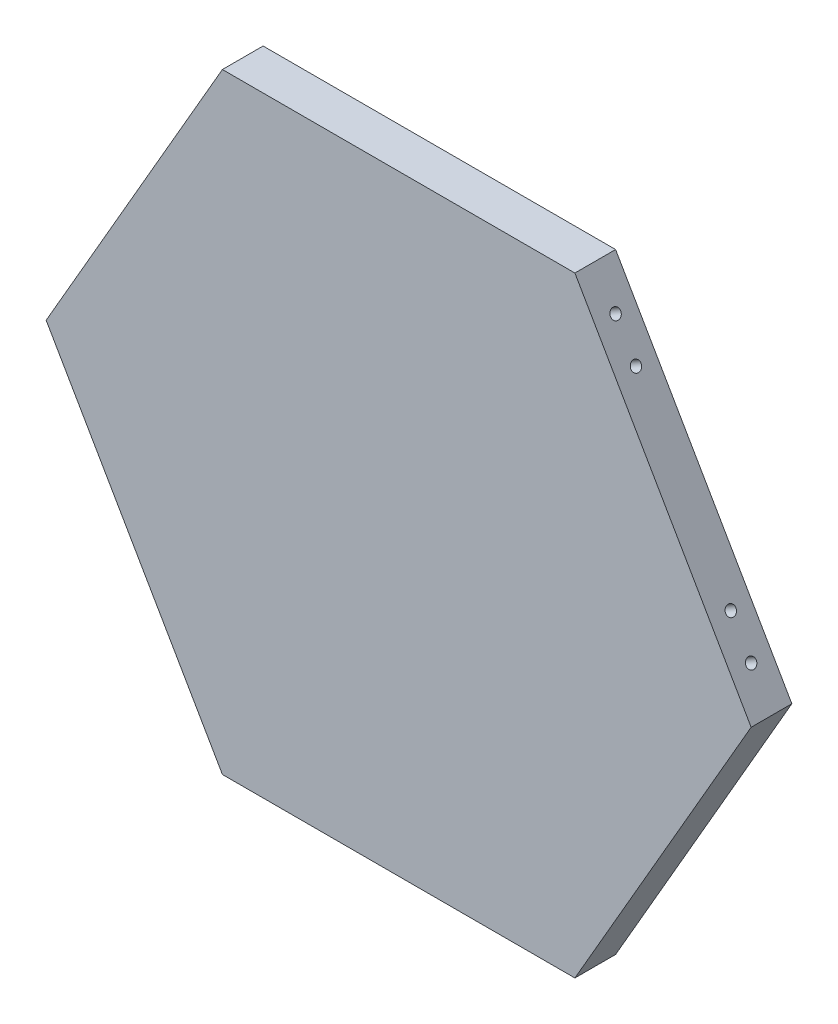
SolidWorks part; units mm, degrees
ref_plane "Top Plane" through (0, 0, 0) normal (0, 0, 1) x (1, 0, 0)
ref_plane "Front Plane" through (0, 0, 0) normal (0, 1, 0) x (1, 0, 0)
ref_plane "Right Plane" through (0, 0, 0) normal (1, 0, 0) x (0, 0, -1)
sketch "Sketch1" plane through (0, 0, 0) normal (0, 0, 1) x (1, 0, 0)
  line L0 (0, 0) -> (163.1642, 0) construction
  line L1 (43.3013, -75) -> (86.6025, 0)
  line L2 (86.6025, 0) -> (43.3013, 75)
  line L3 (43.3013, 75) -> (-43.3013, 75)
  line L4 (-43.3013, 75) -> (-86.6025, 0)
  line L5 (-86.6025, 0) -> (-43.3013, -75)
  line L6 (-43.3013, -75) -> (43.3013, -75)
  circle A0 centre (0, 0) radius 75 construction
  point P11 (86.6025, 0)
  dimension "D1" = 150
extrude "Boss-Extrude1" add sketch "Sketch1" along normal blind 10
sketch "Sketch2" plane through (0, -75, 0) normal (0, -1, 0) x (1, 0, 0)
  line L0 (-43.3013, 10) -> (-43.3013, 0) construction
  line L1 (-43.3013, 0) -> (43.3013, 0) construction
  line L2 (0, 0) -> (0, 18.7567) construction
  circle A0 centre (-33.3013, 5) radius 1.25
  circle A1 centre (-23.3013, 5) radius 1.25
  circle A2 centre (33.3013, 5) radius 1.25
  circle A3 centre (23.3013, 5) radius 1.25
  dimension "D1" = 2.5
  dimension "D3" = 10
  dimension "D2" = 10
  dimension "D4" = 5
extrude "Cut-Extrude1" cut sketch "Sketch2" against normal blind 5
pattern_circular "CirPattern1" count 3 over 360 about axis through (0, 0, 10) along (0, 0, 1) of "Cut-Extrude1"
